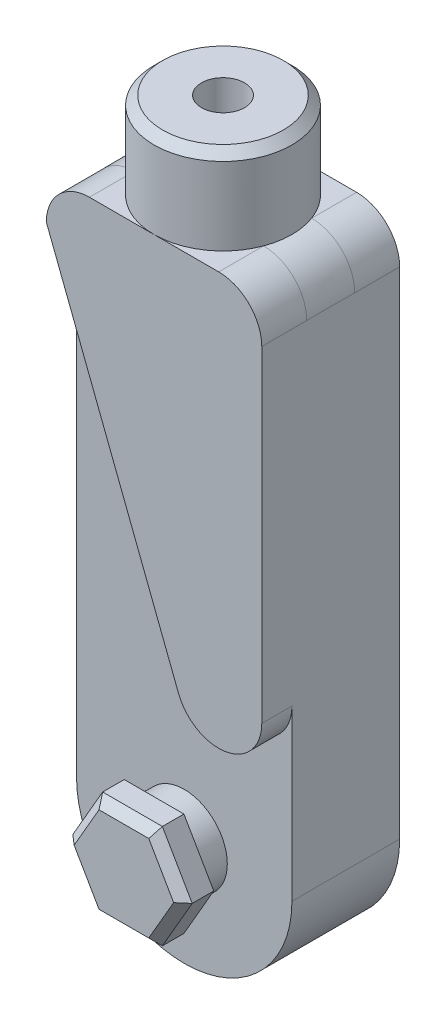
SolidWorks part; units mm, degrees
material "6061-T4 (SS)"
ref_plane "Alzado" through (0, 0, 0) normal (0, 0, 1) x (1, 0, 0)
ref_plane "Planta" through (0, 0, 0) normal (0, 1, 0) x (1, 0, 0)
ref_plane "Vista lateral" through (0, 0, 0) normal (1, 0, 0) x (0, 0, -1)
sketch "Croquis1" plane through (0, 0, 0) normal (0, 0, 1) x (1, 0, 0)
  line L1 (-12.5, -30) -> (12.5, -30)
  line L2 (-12.5, -30) -> (-12.5, 30)
  line L3 (-12.5, 30) -> (12.5, 30)
  line L4 (12.5, -30) -> (12.5, 30)
  line L5 (-12.5, -30) -> (12.5, 30) construction
  line L6 (-12.5, 30) -> (12.5, -30) construction
  line L7 (-12.5, 17.5) -> (12.5, 17.5)
  line L8 (-12.5, 17.5) -> (-12.5, 42.5)
  line L9 (-12.5, 42.5) -> (12.5, 42.5)
  line L10 (12.5, 17.5) -> (12.5, 42.5)
  line L11 (-12.5, 17.5) -> (12.5, 42.5) construction
  line L12 (-12.5, 42.5) -> (12.5, 17.5) construction
  circle A0 centre (0, -30) radius 12.5
  point P0 (0, 0)
  point P8 (0, 30)
  dimension "D1" = 25
  dimension "D2" = 60
  dimension "D3" = 25
extrude "Saliente-Extruir2" add sketch "Croquis1" along normal blind 16 contours L3 L10 L9 L8 | L2 L7 L4 L3 | A0 L4 L7 L2 | L1 A0 | L1 A0 region at (0, -24.6948, 0) region at (0, -1.4445, 0) region at (0, -35.3052, 0) region at (0, 23.75, 0) region at (0, 36.25, 0)
sketch "Croquis2" plane through (0, 0, 16) normal (0, 0, 1) x (1, 0, 0)
  line L0 (-12.5, -30) -> (12.5, -30)
  circle A0 centre (0, -30) radius 12.5
  circle A1 centre (0, -30) radius 5
  arc M3 (-12.5, -30) -> (12.5, -30) centre (0, -30) ccw
extrude "Cortar-Extruir3" cut sketch "Croquis2" against normal blind 3.5 contours A1 L0 A0 | A1 L0 M3 region at (0, -24.0885, 16) region at (0, -35.9115, 16)
fillet "Redondeo5" radius 5 1 edges at (-12.5, -30, 14.25)
fillet "Redondeo6" radius 5 1 edges at (12.5, -30, 14.25)
sketch "Croquis3" plane through (0, 0, 16) normal (0, 0, 1) x (1, 0, 0)
  line L1 (6.9282, -30) -> (3.4641, -24)
  line L2 (3.4641, -24) -> (-3.4641, -24)
  line L3 (-3.4641, -24) -> (-6.9282, -30)
  line L4 (-6.9282, -30) -> (-3.4641, -36)
  line L5 (-3.4641, -36) -> (3.4641, -36)
  line L6 (3.4641, -36) -> (6.9282, -30)
  circle A0 centre (0, -30) radius 6 construction
extrude "Saliente-Extruir3" add sketch "Croquis3" along normal blind 3.5
chamfer "Chaflán1" distance 1 angle 45 1 edges at (5.1962, -27, 19.5)
chamfer "Chaflán2" distance 1 angle 45 1 edges at (-0.5774, -24, 19.5)
chamfer "Chaflán3" distance 1 angle 45 1 edges at (4.9075, -33.5, 19.5)
chamfer "Chaflán4" distance 1 angle 45 1 edges at (-0.5774, -36, 19.5)
chamfer "Chaflán5" distance 1 angle 45 1 edges at (-5.4848, -32.5, 19.5)
chamfer "Chaflán6" distance 1 angle 45 1 edges at (-5.1962, -27, 19.5)
sketch "Croquis4" plane through (0, 42.5, 0) normal (0, 1, 0) x (1, 0, 0)
  line L0 (0, 0) -> (0, -16)
  line L1 (3.4641, -16) -> (-3.4641, -16) construction
  line L2 (-12.5, -8) -> (12.5, -8)
  line L3 (-12.5, -16) -> (-12.5, 0) construction
  line L4 (12.5, -16) -> (12.5, 0) construction
  circle A0 centre (0, -8) radius 8
  line M2 (12.5, 0) -> (-12.5, 0)
  line M3 (-12.5, 0) -> (-12.5, -16)
  line M4 (-12.5, -16) -> (12.5, -16)
  line M5 (12.5, -16) -> (12.5, 0)
extrude "Cortar-Extruir5" cut sketch "Croquis4" against normal blind 10 contours A0 L2 M2 M3 | A0 L2 M3 M4 | A0 L2 M4 M5 | A0 L2 M5 M2 region at (9.1352, 42.5, 3.3888) region at (-9.1352, 42.5, 3.3888) region at (9.1352, 42.5, 12.6112) region at (-9.1352, 42.5, 12.6112)
fillet "Redondeo9" radius 5 1 edges at (12.5, 32.5, 8)
fillet "Redondeo10" radius 5 1 edges at (-12.5, 32.5, 8)
sketch "Croquis5" plane through (0, 42.5, 0) normal (0, 1, 0) x (1, 0, 0)
  line L0 (0, 0) -> (0, -16)
  line L1 (3.4641, -16) -> (-3.4641, -16) construction
  line L2 (-8, -8) -> (8, -8)
  arc A0 (-7.5, -5.2161) -> (-7.5, -10.7839) centre (0, -8) ccw construction
  arc A1 (7.5, -10.7839) -> (7.5, -5.2161) centre (0, -8) ccw construction
  circle A2 centre (0, -8) radius 2.5
extrude "Cortar-Extruir6" cut sketch "Croquis5" against normal blind 5 contours A2
chamfer "Chaflán7" distance 1 angle 45 1 edges at (0, 42.5, 16)
sketch "Croquis6" plane through (0, 0, 16) normal (0, 0, 1) x (1, 0, 0)
  line L0 (12.5, 27.5) -> (12.5, -14.1886)
  line L1 (2.5, 27.5) -> (-5.3571, -18.7062)
  line L2 (-5.3571, -18.7062) -> (7.5, -19.1886)
  line L3 (12.5, -30) -> (12.5, 27.5)
  line L4 (12.5, -14.1886) -> (12.5, 27.5)
  circle A0 centre (7.5, -14.1886) radius 5
  circle A1 centre (7.5, 27.5) radius 5
  circle A2 centre (0, -30) radius 5
  circle A3 centre (0, -30) radius 12.5
  arc A4 (-5.3571, -18.7062) -> (5.3571, -18.7062) centre (0, -30) cw
sketch "Croquis7" plane through (0, 0, 16) normal (0, 0, 1) x (1, 0, 0)
  line L0 (-12.5, 27.5) -> (5.3571, -18.7062)
  line L1 (-12.5, -14.1886) -> (-12.5, 27.5)
  arc A0 (5.3571, -18.7062) -> (-5.3571, -18.7062) centre (0, -30) ccw
  arc A1 (-5.3571, -18.7062) -> (-12.5, -14.1886) centre (-7.5, -14.1886) cw
extrude "Cortar-Extruir9" cut sketch "Croquis7" against normal blind 3.5
fillet "Redondeo12" radius 5 1 edges at (5.3571, -18.7062, 14.25)
